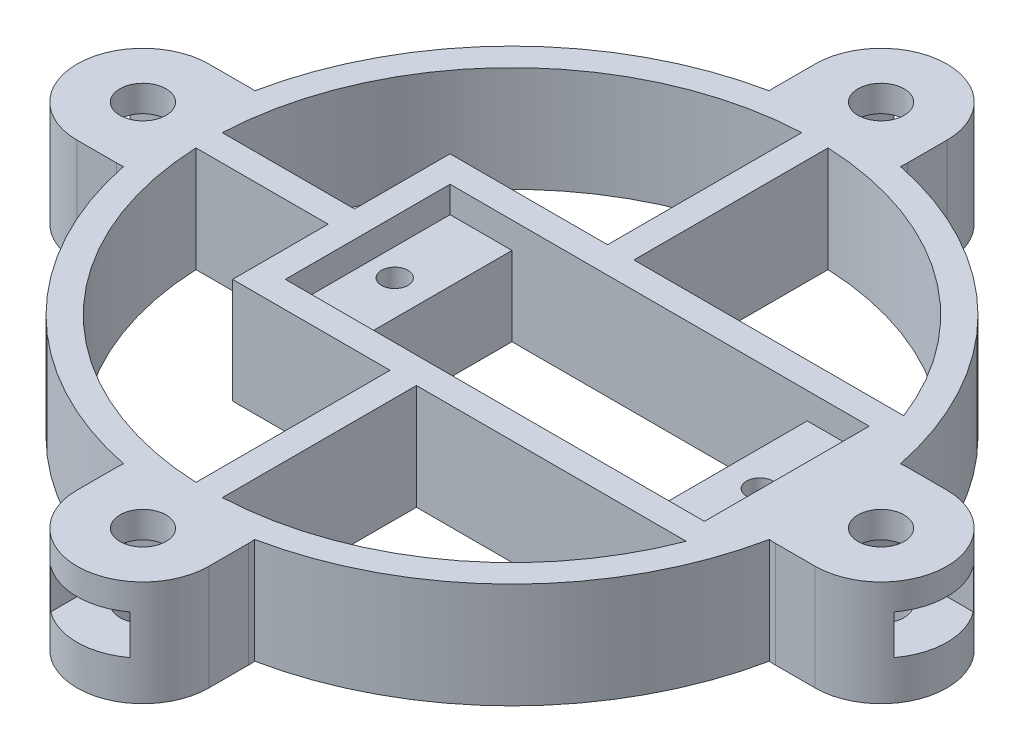
SolidWorks part; units mm, degrees
ref_plane "Front Plane" through (0, 0, 0) normal (0, 0, 1) x (1, 0, 0)
ref_plane "Top Plane" through (0, 0, 0) normal (0, 1, 0) x (1, 0, 0)
ref_plane "Right Plane" through (0, 0, 0) normal (1, 0, 0) x (0, 0, -1)
sketch "Sketch2" plane through (0, 0, 0) normal (0, 1, 0) x (1, 0, 0)
  line L0 (0, 0) -> (0, 25) construction
  circle A0 centre (0, 0) radius 25
  dimension "D1" = 50
extrude "Boss-Extrude1" add sketch "Sketch2" along normal blind 8
sketch "Sketch3" plane through (0, 8, 0) normal (0, 1, 0) x (1, 0, 0)
  line L0 (0, 25) -> (0, 0) construction
  line L1 (0, 0) -> (25, 0) construction
  line L2 (-10.95, 6.25) -> (20.85, 6.25)
  line L3 (20.85, 6.25) -> (20.85, -6.25)
  line L4 (-10.95, 6.25) -> (-10.95, -6.25)
  line L5 (-10.95, -6.25) -> (20.85, -6.25)
  circle A0 centre (0, 0) radius 25 construction
  point P12 (20.85, 0)
  point P13 (-10.95, 0)
  dimension "D1" = 31.8
  dimension "D2" = 10.95
  dimension "D3" = 12.5
extrude "Cut-Extrude1" cut sketch "Sketch3" against normal blind 2
sketch "Sketch4" plane through (0, 6, 0) normal (0, 1, 0) x (1, 0, 0)
  line L0 (4.95, 6.25) -> (4.95, -6.25) construction
  line L1 (20.85, 6.25) -> (-10.95, 6.25) construction
  line L2 (-10.95, -6.25) -> (20.85, -6.25) construction
  line L4 (-6.25, 6.25) -> (16.15, 6.25)
  line L5 (-6.25, 6.25) -> (-6.25, -6.25)
  line L6 (-6.25, -6.25) -> (16.15, -6.25)
  line L7 (16.15, 6.25) -> (16.15, -6.25)
  line L8 (-6.25, 6.25) -> (16.15, -6.25) construction
  line L9 (-6.25, -6.25) -> (16.15, 6.25) construction
  point P6 (4.95, 0)
  dimension "D1" = 22.4
extrude "Cut-Extrude2" cut sketch "Sketch4" against normal through all
sketch "Sketch6" plane through (0, 6, 0) normal (0, 1, 0) x (1, 0, 0)
  line L0 (-10.95, 0) -> (20.85, 0) construction
  line L1 (-10.95, 6.25) -> (-10.95, -6.25) construction
  line L2 (20.85, -6.25) -> (20.85, 6.25) construction
  line L3 (4.95, 6.25) -> (4.95, -6.25) construction
  line L4 (20.85, 6.25) -> (-10.95, 6.25) construction
  line L5 (-10.95, -6.25) -> (20.85, -6.25) construction
  circle A0 centre (-8.9, 0) radius 1
  circle A1 centre (18.8, 0) radius 1
  dimension "D1" = 2
  dimension "D2" = 27.7
extrude "Cut-Extrude4" cut sketch "Sketch6" against normal through all
sketch "Sketch9" plane through (0, 8, 0) normal (0, 1, 0) x (1, 0, 0)
  line L0 (-10.95, 6.25) -> (-10.95, -6.25) construction
  line L1 (-12.95, 8.25) -> (-1, 8.25)
  line L2 (-12.95, 8.25) -> (-12.95, 1)
  line L3 (-12.95, -8.25) -> (-1, -8.25)
  line L4 (-12.95, 1) -> (-22.9783, 1)
  line L6 (20.85, 6.25) -> (-10.95, 6.25) construction
  line L7 (0, 0) -> (-31.825, 0) construction
  line L8 (0, 0) -> (0, 31.7606) construction
  line L9 (-1, 22.9783) -> (-1, 8.25)
  line L10 (1, 22.9783) -> (1, 8.25)
  line L11 (-12.95, -1) -> (-22.9783, -1)
  line L12 (1, -22.9783) -> (1, -8.25)
  line L13 (-1, -22.9783) -> (-1, -8.25)
  line L14 (-12.95, -1) -> (-12.95, -8.25)
  line L15 (1, 8.25) -> (21.4695, 8.25)
  line L16 (1, -8.25) -> (21.4695, -8.25)
  arc A0 (21.4695, 8.25) -> (1, 22.9783) centre (0, 0) ccw
  arc A1 (-22.9783, -1) -> (-1, -22.9783) centre (0, 0) ccw
  arc A2 (-1, 22.9783) -> (-22.9783, 1) centre (0, 0) ccw
  arc A3 (1, -22.9783) -> (21.4695, -8.25) centre (0, 0) ccw
  dimension "D1" = 46
  dimension "D2" = 2
  dimension "D4" = 2
  dimension "D5" = 2
  dimension "D6" = 2
extrude "Cut-Extrude5" cut sketch "Sketch9" against normal through all
sketch "Sketch10" plane through (0, 8, 0) normal (0, 1, 0) x (1, 0, 0)
  line L0 (-25, 0) -> (-28, 0) construction
  line L1 (-25, -5) -> (-28, -5)
  line L2 (-25, 5) -> (-28, 5)
  line L3 (0, 0) -> (0, 32.9015) construction
  line L4 (-25, -5) -> (-28, -5)
  line L5 (-25, 5) -> (-28, 5)
  line L6 (-25, -5) -> (-28, -5)
  line L7 (-25, 5) -> (-28, 5)
  line L8 (-25, -5) -> (-28, -5)
  line L9 (-25, 5) -> (-28, 5)
  line L10 (-5, 25) -> (-5, 28)
  line L11 (5, 25) -> (5, 28)
  line L12 (-5, 25) -> (-5, 28)
  line L13 (5, 25) -> (5, 28)
  line L14 (-5, 25) -> (-5, 28)
  line L15 (5, 25) -> (5, 28)
  line L16 (-5, 25) -> (-5, 28)
  line L17 (5, 25) -> (5, 28)
  line L18 (0, 25) -> (0, 28) construction
  line L19 (25, 5) -> (28, 5)
  line L20 (25, -5) -> (28, -5)
  line L21 (25, 5) -> (28, 5)
  line L22 (25, -5) -> (28, -5)
  line L23 (25, 5) -> (28, 5)
  line L24 (25, -5) -> (28, -5)
  line L25 (25, 5) -> (28, 5)
  line L26 (25, -5) -> (28, -5)
  line L27 (25, 0) -> (28, 0) construction
  line L28 (5, -25) -> (5, -28)
  line L29 (-5, -25) -> (-5, -28)
  line L30 (5, -25) -> (5, -28)
  line L31 (-5, -25) -> (-5, -28)
  line L32 (5, -25) -> (5, -28)
  line L33 (-5, -25) -> (-5, -28)
  line L34 (5, -25) -> (5, -28)
  line L35 (-5, -25) -> (-5, -28)
  line L36 (0, -25) -> (0, -28) construction
  circle A0 centre (0, 0) radius 25 construction
  arc A1 (-25, -5) -> (-24.5, -4.9749) centre (-25, 0) ccw
  arc A2 (-28, 5) -> (-28, -5) centre (-28, 0) ccw
  arc A3 (-24.5, 4.9749) -> (-24.5, -4.9749) centre (0, 0) ccw
  arc A4 (-24.5, 4.9749) -> (-25, 5) centre (-25, 0) ccw
  arc A5 (-24.5, -4.9749) -> (-25, -5) centre (-25, 0) cw
  arc A6 (-25, 5) -> (-24.5, 4.9749) centre (-25, 0) cw
  arc A7 (-5, 25) -> (-4.9749, 24.5) centre (0, 25) ccw
  arc A8 (-25, -5) -> (-24.5, -4.9749) centre (-25, 0) ccw
  arc A9 (-24.5, 4.9749) -> (-25, 5) centre (-25, 0) ccw
  arc A10 (-24.5, -4.9749) -> (-25, -5) centre (-25, 0) cw
  arc A11 (-25, 5) -> (-24.5, 4.9749) centre (-25, 0) cw
  arc A12 (5, 28) -> (-5, 28) centre (0, 28) ccw
  arc A13 (4.9749, 24.5) -> (-4.9749, 24.5) centre (0, 0) ccw
  arc A14 (4.9749, 24.5) -> (5, 25) centre (0, 25) ccw
  arc A15 (-4.9749, 24.5) -> (-5, 25) centre (0, 25) cw
  arc A16 (5, 25) -> (4.9749, 24.5) centre (0, 25) cw
  arc A17 (-5, 25) -> (-4.9749, 24.5) centre (0, 25) ccw
  arc A18 (4.9749, 24.5) -> (5, 25) centre (0, 25) ccw
  arc A19 (-4.9749, 24.5) -> (-5, 25) centre (0, 25) cw
  arc A20 (5, 25) -> (4.9749, 24.5) centre (0, 25) cw
  arc A21 (25, 5) -> (24.5, 4.9749) centre (25, 0) ccw
  arc A22 (28, -5) -> (28, 5) centre (28, 0) ccw
  arc A23 (24.5, -4.9749) -> (24.5, 4.9749) centre (0, 0) ccw
  arc A24 (24.5, -4.9749) -> (25, -5) centre (25, 0) ccw
  arc A25 (24.5, 4.9749) -> (25, 5) centre (25, 0) cw
  arc A26 (25, -5) -> (24.5, -4.9749) centre (25, 0) cw
  arc A27 (25, 5) -> (24.5, 4.9749) centre (25, 0) ccw
  arc A28 (24.5, -4.9749) -> (25, -5) centre (25, 0) ccw
  arc A29 (24.5, 4.9749) -> (25, 5) centre (25, 0) cw
  arc A30 (25, -5) -> (24.5, -4.9749) centre (25, 0) cw
  arc A31 (5, -25) -> (4.9749, -24.5) centre (0, -25) ccw
  arc A32 (-5, -28) -> (5, -28) centre (0, -28) ccw
  arc A33 (-4.9749, -24.5) -> (4.9749, -24.5) centre (0, 0) ccw
  arc A34 (-4.9749, -24.5) -> (-5, -25) centre (0, -25) ccw
  arc A35 (4.9749, -24.5) -> (5, -25) centre (0, -25) cw
  arc A36 (-5, -25) -> (-4.9749, -24.5) centre (0, -25) cw
  arc A37 (5, -25) -> (4.9749, -24.5) centre (0, -25) ccw
  arc A38 (-4.9749, -24.5) -> (-5, -25) centre (0, -25) ccw
  arc A39 (4.9749, -24.5) -> (5, -25) centre (0, -25) cw
  arc A40 (-5, -25) -> (-4.9749, -24.5) centre (0, -25) cw
  point P6 (-26.5, 0)
  point P20 (0, 26.5)
  point P29 (26.5, 0)
  point P38 (0, -26.5)
  point P45 (0, 0)
  dimension "D2" = 5
  dimension "D3" = 4
  dimension "D1" = 3
extrude "Boss-Extrude3" add sketch "Sketch10" against normal up to surface (8 mm away) contours A5 A24 L20 A22 L19 A21 | A5 A34 L29 A32 L28 A31 | A5 A4 L2 A2 L1 A1 | A5 A14 L11 A12 L10 A7 region at (-28.4663, 8, 0) region at (0, 8, -28.4663) region at (28.4663, 8, 0) region at (0, 8, 28.4663) up to face at (8.556, 0, -14.1779)
sketch "Sketch13" plane through (0, 0, 0) normal (0, -1, 0) x (1, 0, 0)
  circle A0 centre (28, 0) radius 1.75
  circle A1 centre (0, -28) radius 1.75
  circle A2 centre (-28, 0) radius 1.75
  circle A3 centre (0, 28) radius 1.75
  point P12 (0, 0)
  dimension "D1" = 3.5
  dimension "D2" = 4
extrude "Cut-Extrude8" cut sketch "Sketch13" against normal through all
ref_plane "Plane2" through (0, 3, 0) normal (0, -1, 0) x (-1, 0, 0)
sketch "Sketch14" plane through (0, 3, 0) normal (0, -1, 0) x (-1, 0, 0)
  line L0 (0, 0) -> (-38.6509, 0) construction
  line L1 (0, 24.5359) -> (3, 26.2679)
  line L2 (-24.5359, 0) -> (-26.2679, 3)
  line L3 (-26.2679, 3) -> (-32, 3)
  line L4 (3, 26.2679) -> (3, 32)
  line L5 (-3, 32) -> (-3, 26.2679)
  line L6 (-32, -3) -> (-26.2679, -3)
  line L7 (-26.2679, -3) -> (-24.5359, 0)
  line L8 (-31.4641, 0) -> (-30.5981, -1.5) [skipped]
  line L9 (-29.7321, 3) -> (-30.5981, 1.5) [skipped]
  line L10 (-3, 26.2679) -> (0, 24.5359)
  line L11 (24.5359, 0) -> (26.2679, -3)
  line L12 (26.2679, -3) -> (32, -3)
  line L13 (32, 3) -> (26.2679, 3)
  line L14 (26.2679, 3) -> (24.5359, 0)
  line L15 (0, -24.5359) -> (-3, -26.2679)
  line L16 (-3, -26.2679) -> (-3, -32)
  line L17 (3, -32) -> (3, -26.2679)
  line L18 (3, -26.2679) -> (0, -24.5359)
  circle A0 centre (-28, 0) radius 3 construction
  arc A1 (-32, 3) -> (-32, -3) centre (-28, 0) ccw
  arc A2 (3, 32) -> (-3, 32) centre (0, 28) ccw
  circle A3 centre (0, 28) radius 3 construction
  arc A4 (32, -3) -> (32, 3) centre (28, 0) ccw
  circle A5 centre (28, 0) radius 3 construction
  arc A6 (-3, -32) -> (3, -32) centre (0, -28) ccw
  circle A7 centre (0, -28) radius 3 construction
  point P39 (0, 0)
  dimension "D1" = 6
  dimension "D2" = 10
  dimension "D3" = 4
extrude "Cut-Extrude9" cut sketch "Sketch14" against normal blind 3
